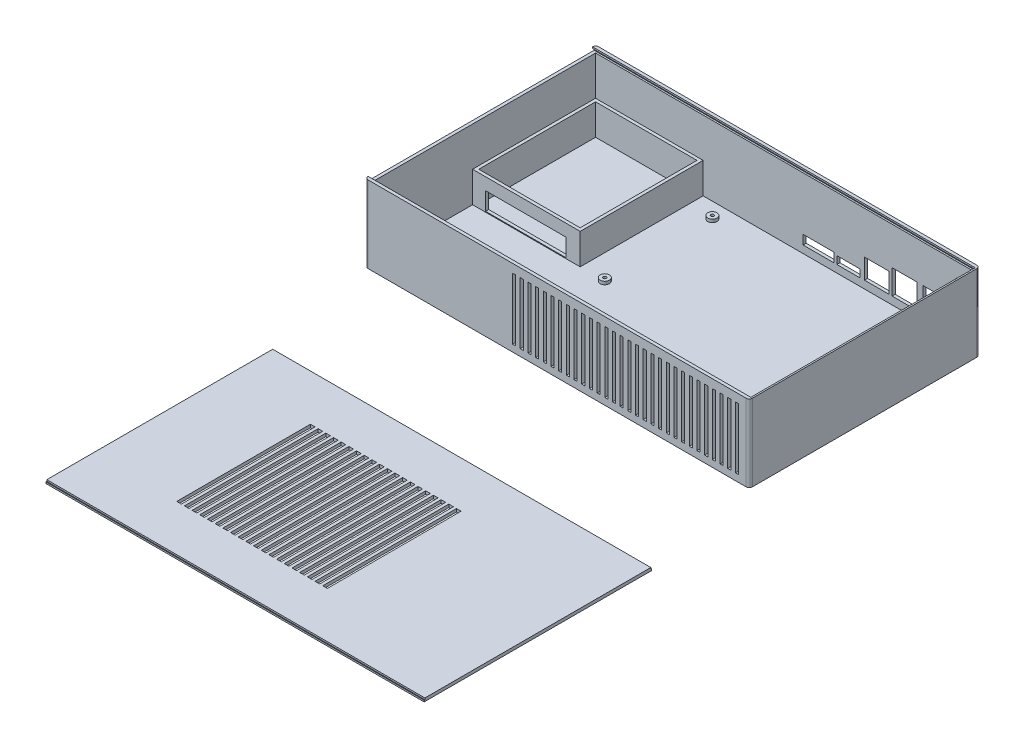
SolidWorks part; units mm, degrees
ref_plane "前视基准面" through (0, 0, 0) normal (0, 0, 1) x (1, 0, 0)
ref_plane "上视基准面" through (0, 0, 0) normal (0, 1, 0) x (1, 0, 0)
ref_plane "右视基准面" through (0, 0, 0) normal (1, 0, 0) x (0, 0, -1)
other "Configuration Table"
sketch "草图1" plane through (0, 0, 0) normal (0, 1, 0) x (1, 0, 0)
  line L1 (-233.2808, 5.2756) -> (12.7192, 5.2756)
  line L2 (-235.2808, 3.2756) -> (-235.2808, -142.7244)
  line L3 (-233.2808, -144.7244) -> (12.7192, -144.7244)
  line L4 (14.7192, 3.2756) -> (14.7192, -142.7244)
  arc A0 (12.7192, 5.2756) -> (14.7192, 3.2756) centre (12.7192, 3.2756) cw
  arc A1 (12.7192, -144.7244) -> (14.7192, -142.7244) centre (12.7192, -142.7244) ccw
  arc A2 (-233.2808, -144.7244) -> (-235.2808, -142.7244) centre (-233.2808, -142.7244) cw
  arc A3 (-233.2808, 5.2756) -> (-235.2808, 3.2756) centre (-233.2808, 3.2756) ccw
  point P6 (14.7192, 5.2756)
  point P9 (14.7192, -144.7244)
  point P14 (-235.2808, 5.2756)
  dimension "D3" = 2
  dimension "D1" = 250
  dimension "D2" = 150
extrude "凸台-拉伸1" add sketch "草图1" along normal blind 50 contours L1 A0 L4 A1 L3 A2 L2 A3
shell "抽壳2" thickness 2 removed face at (-110.2808, 50, 69.7244)
sketch "草图2" plane through (0, 0, -5.2756) normal (0, 0, -1) x (-1, 0, 0)
  line L0 (-14.7192, 50) -> (-14.7192, 0) construction
  line L1 (-9.7192, 17) -> (0.2808, 17)
  line L2 (-9.7192, 17) -> (-9.7192, 7)
  line L3 (-9.7192, 7) -> (0.2808, 7)
  line L4 (0.2808, 17) -> (0.2808, 7)
  line L5 (-9.7192, 17) -> (0.2808, 7) construction
  line L6 (-9.7192, 7) -> (0.2808, 17) construction
  line L7 (233.2808, 0) -> (-12.7192, 0) construction
  line L9 (4.2808, 23) -> (20.2808, 23)
  line L10 (4.2808, 23) -> (4.2808, 7)
  line L11 (4.2808, 7) -> (20.2808, 7)
  line L12 (20.2808, 23) -> (20.2808, 7)
  line L13 (4.2808, 23) -> (20.2808, 7) construction
  line L14 (4.2808, 7) -> (20.2808, 23) construction
  line L15 (24.2808, 7) -> (40.2808, 7)
  line L16 (24.2808, 7) -> (24.2808, 23)
  line L17 (24.2808, 23) -> (40.2808, 23)
  line L18 (40.2808, 7) -> (40.2808, 23)
  line L19 (24.2808, 7) -> (40.2808, 23) construction
  line L20 (24.2808, 23) -> (40.2808, 7) construction
  line L21 (42.2808, 20) -> (58.2808, 20)
  line L22 (42.2808, 20) -> (42.2808, 7)
  line L23 (42.2808, 7) -> (58.2808, 7)
  line L24 (58.2808, 20) -> (58.2808, 7)
  line L25 (42.2808, 20) -> (58.2808, 7) construction
  line L26 (42.2808, 7) -> (58.2808, 20) construction
  line L27 (61.2808, 11.8292) -> (76.2808, 11.8292)
  line L28 (61.2808, 11.8292) -> (61.2808, 6.8292)
  line L29 (61.2808, 6.8292) -> (76.2808, 6.8292)
  line L30 (76.2808, 11.8292) -> (76.2808, 6.8292)
  line L31 (78.2808, 6.8292) -> (98.2808, 6.8292)
  line L32 (78.2808, 6.8292) -> (78.2808, 12.8292)
  line L33 (78.2808, 12.8292) -> (98.2808, 12.8292)
  line L34 (98.2808, 6.8292) -> (98.2808, 12.8292)
  point P0 (-4.7192, 12)
  point P9 (12.2808, 15)
  point P14 (32.2808, 15)
  point P19 (50.2808, 13.5)
  point P32 (78.2808, 9.8292)
  dimension "D1" = 10
  dimension "D2" = 10
  dimension "D3" = 5
  dimension "D4" = 7
  dimension "D5" = 16
  dimension "D6" = 16
  dimension "D7" = 4
  dimension "D8" = 16
  dimension "D9" = 16
  dimension "D10" = 7
  dimension "D11" = 4
  dimension "D12" = 13
  dimension "D13" = 16
  dimension "D14" = 2
  dimension "D15" = 15
  dimension "D16" = 5
  dimension "D17" = 3
  dimension "D18" = 6
  dimension "D19" = 20
  dimension "D20" = 2
extrude "切除-拉伸1" cut sketch "草图2" against normal blind 50
sketch "草图4" plane through (0, 0, -5.2756) normal (0, 0, -1) x (-1, 0, 0)
  line L1 (-9.268, 38.0037) -> (-1.268, 38.0037)
  line L2 (-9.268, 38.0037) -> (-9.268, 30.0037)
  line L3 (-9.268, 30.0037) -> (-1.268, 30.0037)
  line L4 (-1.268, 38.0037) -> (-1.268, 30.0037)
  dimension "D1" = 8
  dimension "D2" = 8
extrude "切除-拉伸2" cut sketch "草图4" against normal blind 50
sketch "草图5" plane through (0, 2, 0) normal (0, 1, 0) x (1, 0, 0)
  line L0 (12.7192, 3.2756) -> (12.7192, -142.7244) construction
  line L1 (-233.2808, 3.2756) -> (12.7192, 3.2756) construction
  line L10 (-231.2808, 1.2756) -> (-231.2808, -140.7244)
  line L11 (-231.2808, -140.7244) -> (10.7192, -140.7244)
  line L12 (10.7192, -140.7244) -> (10.7192, 1.2756)
  line L13 (10.7192, 1.2756) -> (-231.2808, 1.2756)
  line L14 (-231.2808, 1.2756) -> (-231.2808, -140.7244)
  line L15 (-231.2808, -140.7244) -> (10.7192, -140.7244)
  line L16 (10.7192, -140.7244) -> (10.7192, 1.2756)
  line L17 (10.7192, 1.2756) -> (-231.2808, 1.2756)
  circle A0 centre (7.7192, -81.7244) radius 1
  circle A1 centre (-7.2808, -31.7244) radius 1
  circle A2 centre (-147.2808, -6.7244) radius 1
  circle A3 centre (-147.2808, -76.7244) radius 1
  circle A4 centre (-147.2808, -6.7244) radius 3
  circle A5 centre (-147.2808, -76.7244) radius 3
  circle A6 centre (7.7192, -81.7244) radius 3
  circle A7 centre (-7.2808, -31.7244) radius 3
  dimension "D1" = 2
  dimension "D4" = 2
  dimension "D7" = 2
  dimension "D10" = 2
  dimension "D2" = 5
  dimension "D3" = 85
  dimension "D5" = 20
  dimension "D6" = 35
  dimension "D8" = 10
  dimension "D9" = 160
  dimension "D11" = 70
  dimension "D12" = 2
  dimension "D13" = 2
  dimension "D14" = 2
extrude "凸台-拉伸2" add sketch "草图5" along normal blind 2 contours A4 A2 | A5 A3 | A7 A1 | A6 A0 region at (4.8041, 2, 81.7244) region at (-150.1959, 2, 6.7244) region at (-150.1959, 2, 76.7244) region at (-10.1959, 2, 31.7244)
sketch "草图7" plane through (-235.2808, 0, 0) normal (-1, 0, 0) x (0, 0, 1)
  line L2 (-4.3291, 49) -> (-4.3291, 47.5)
  line L3 (-4.3291, 47.5) -> (143.8215, 47.5)
  line L4 (143.8215, 49) -> (143.8215, 47.5)
  line L5 (142.7244, 50) -> (142.7244, 0) construction
  line L6 (-3.2756, 50) -> (142.7244, 50)
  line L7 (-3.2756, 50) -> (-3.2756, 49)
  line L9 (142.7244, 50) -> (142.7244, 49)
  line L10 (-4.3291, 49) -> (-3.2756, 49)
  line L11 (142.7244, 49) -> (143.8215, 49)
  dimension "D1" = 1.5
extrude "切除-拉伸7" cut sketch "草图7" against normal blind 249
sketch "草图19" plane through (0, 2, 0) normal (0, 1, 0) x (1, 0, 0)
  line L0 (-231.2808, 1.2756) -> (-231.2808, -74.7244)
  line L1 (-233.2808, 3.2756) -> (-163.2808, 3.2756)
  line L2 (-233.2808, 3.2756) -> (-233.2808, -76.7244)
  line L3 (-233.2808, -76.7244) -> (-163.2808, -76.7244)
  line L4 (-163.2808, 3.2756) -> (-163.2808, -76.7244)
  line L5 (-231.2808, -74.7244) -> (-165.2808, -74.7244)
  line L6 (-165.2808, 1.2756) -> (-165.2808, -74.7244)
  line L7 (-231.2808, 1.2756) -> (-165.2808, 1.2756)
  dimension "D1" = 80
  dimension "D2" = 70
  dimension "D3" = 2
extrude "凸台-拉伸3" add sketch "草图19" along normal blind 20
sketch "草图22" plane through (0, 0, 76.7244) normal (0, 0, 1) x (1, 0, 0)
  line L1 (-224.8397, 14.1364) -> (-172.4257, 14.1364)
  line L2 (-224.8397, 14.1364) -> (-224.8397, 2.5501)
  line L3 (-224.8397, 2.5501) -> (-172.4257, 2.5501)
  line L4 (-172.4257, 14.1364) -> (-172.4257, 2.5501)
extrude "切除-拉伸9" cut sketch "草图22" against normal blind 20
sketch "草图25" plane through (0, 0, 0) normal (0, 1, 0) x (1, 0, 0)
  line L1 (-217.9011, -221.6455) -> (28.0989, -221.6455)
  line L2 (-217.9011, -221.6455) -> (-217.9011, -369.6455)
  line L3 (-217.9011, -369.6455) -> (28.0989, -369.6455)
  line L4 (28.0989, -221.6455) -> (28.0989, -369.6455)
  dimension "D1" = 246
  dimension "D2" = 148
extrude "凸台-拉伸4" add sketch "草图25" against normal blind 1 separate body contours L2 L3 L4 L1
sketch "草图27" plane through (-217.9011, 0, 0) normal (-1, 0, 0) x (0, 0, 1)
  line L0 (221.6455, 0) -> (369.6455, 0) construction
  line L1 (222.1455, 0) -> (369.1455, 0)
  line L2 (222.1455, 0) -> (222.1455, 1)
  line L3 (222.1455, 1) -> (369.1455, 1)
  line L4 (369.1455, 0) -> (369.1455, 1)
  line L5 (221.6455, -1) -> (221.6455, 0) construction
  line L6 (369.6455, -1) -> (369.6455, 0) construction
  dimension "D1" = 1
  dimension "D2" = 0.5
  dimension "D3" = 0.5
extrude "凸台-拉伸5" add sketch "草图27" against normal blind 246
sketch "草图29" plane through (0, 0, 144.7244) normal (0, 0, 1) x (1, 0, 0)
  line L0 (12.7192, 50) -> (12.7192, 0) construction
  line L1 (5.7192, 44.4403) -> (7.7192, 44.4403)
  line L2 (5.7192, 44.4403) -> (5.7192, 4.4403)
  line L3 (5.7192, 4.4403) -> (7.7192, 4.4403)
  line L4 (7.7192, 44.4403) -> (7.7192, 4.4403)
  dimension "D1" = 2
  dimension "D2" = 40
  dimension "D3" = 5
extrude "切除-拉伸10" cut sketch "草图29" against normal blind 59
pattern_linear "阵列(线性)4" count 30 spacing 5 along (-1, 0, 0) of "切除-拉伸10"
sketch "草图30" plane through (0, 1, 0) normal (0, 1, 0) x (1, 0, 0)
  line L0 (28.0989, -369.1455) -> (-217.9011, -369.1455) construction
  line L1 (-163.3551, -252.1455) -> (-160.3551, -252.1455)
  line L2 (-163.3551, -252.1455) -> (-163.3551, -339.1455)
  line L3 (-163.3551, -339.1455) -> (-160.3551, -339.1455)
  line L4 (-160.3551, -252.1455) -> (-160.3551, -339.1455)
  line L5 (28.0989, -222.1455) -> (-217.9011, -222.1455) construction
  dimension "D1" = 3
  dimension "D2" = 30
  dimension "D3" = 30
extrude "切除-拉伸12" cut sketch "草图30" against normal blind 59
pattern_linear "阵列(线性)7" count 20 spacing 5 along (1, 0, 0) of "切除-拉伸12"
